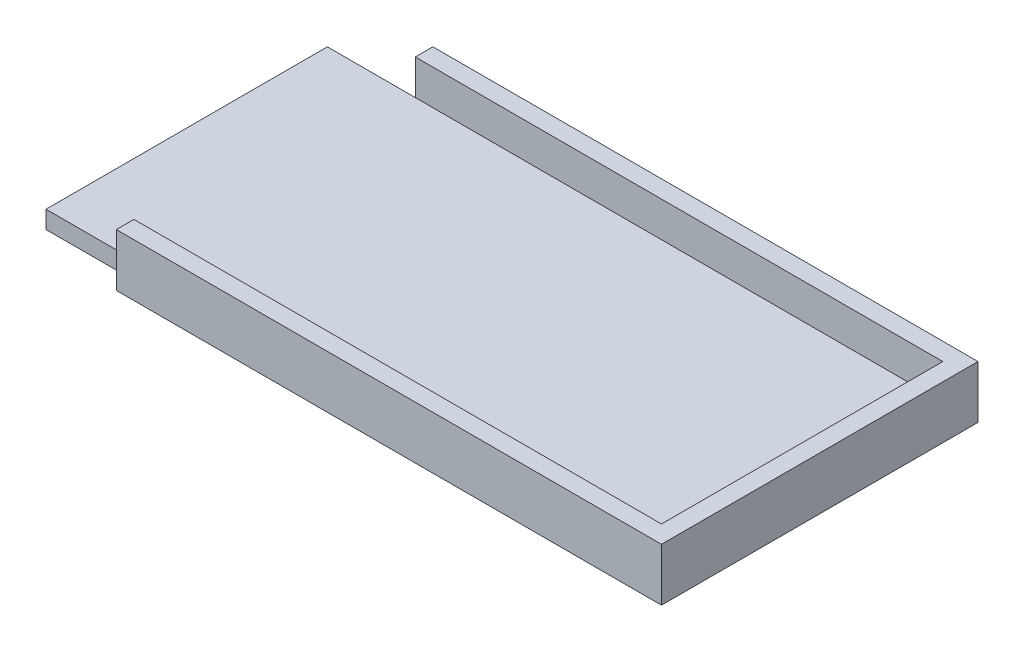
SolidWorks part; units mm, degrees
ref_plane "Front Plane" through (0, 0, 0) normal (0, 0, 1) x (1, 0, 0)
ref_plane "Top Plane" through (0, 0, 0) normal (0, 1, 0) x (1, 0, 0)
ref_plane "Right Plane" through (0, 0, 0) normal (1, 0, 0) x (0, 0, -1)
sketch "Sketch1" plane through (0, 0, 0) normal (0, 1, 0) x (1, 0, 0)
  line L1 (30, -16) -> (-30, -16)
  line L2 (30, -16) -> (30, 16)
  line L3 (30, 16) -> (-30, 16)
  line L4 (-30, -16) -> (-30, 16)
  line L5 (30, -16) -> (-30, 16) construction
  line L6 (30, 16) -> (-30, -16) construction
  point P0 (0, 0)
  dimension "D1" = 60
  dimension "D2" = 32
extrude "Boss-Extrude1" add sketch "Sketch1" along normal blind 2
sketch "Sketch2" plane through (0, 0, 0) normal (0, -1, 0) x (1, 0, 0)
  line L1 (-30, -18) -> (32, -18)
  line L2 (32, -18) -> (32, 18)
  line L3 (32, 18) -> (-30, 18)
  line L4 (-30, 16) -> (-30, -16)
  line L5 (-30, -16) -> (30, -16)
  line L6 (30, -16) -> (30, 16)
  line L7 (30, 16) -> (-30, 16)
  line L9 (-30, -16) -> (30, -16)
  line L10 (30, -16) -> (30, 16)
  line L11 (30, 16) -> (-30, 16)
  line L12 (-32, 18) -> (-32, -18) construction
  line L13 (-30, 16) -> (-30, -16) construction
  line L14 (-30, 16) -> (-30, 18)
  line L15 (-30, -16) -> (-30, -18)
  line L17 (32, 18) -> (-32, 18) construction
  line L18 (-32, -18) -> (32, -18) construction
  dimension "D1" = 0
  dimension "D2" = 2
extrude "Boss-Extrude2" add sketch "Sketch2" along direction (0, -1, 0) on the side against the normal offset from surface (6 mm away) 4 up to face at (0, 2, 0) offset beyond the face yes
sketch "Sketch3" plane through (0, 0, 0) normal (0, -1, 0) x (1, 0, 0)
  line L0 (-30, -18) -> (-30, 18) construction
  line L1 (-30, -16) -> (-40, -16)
  line L2 (-30, -16) -> (-30, 16)
  line L3 (-30, 16) -> (-40, 16)
  line L4 (-40, -16) -> (-40, 16)
  point P6 (-30, 0)
  point P7 (-30, 0)
  dimension "D1" = 32
  dimension "D2" = 10
extrude "Boss-Extrude3" add sketch "Sketch3" against normal blind 2
sketch "Sketch4" [suppressed] plane through (0, 0, 0) normal (0, -1, 0) x (1, 0, 0)
  line L0 (-40, 16) -> (-40, -16) construction
  line L1 (-40, -5) -> (-55, -5)
  line L2 (-40, -5) -> (-40, 5)
  line L3 (-40, 5) -> (-55, 5)
  line L4 (-55, -5) -> (-55, 5)
  point P6 (-40, 0)
  point P7 (-40, 0)
  dimension "D1" = 15
  dimension "D2" = 10
extrude "Boss-Extrude4" [suppressed] add sketch "Sketch4" against normal up to surface (2 mm away) up to face at (-13.3333, 2, 0)
fillet "Fillet1" [suppressed] radius 5
sketch "Sketch5" [suppressed] plane through (0, 0, 0) normal (0, -1, 0) x (1, 0, 0)
  circle A0 centre (-50, 0) radius 3.1
  dimension "D1" = 6.2
extrude "Cut-Extrude1" [suppressed] cut sketch "Sketch5" against normal up to next
